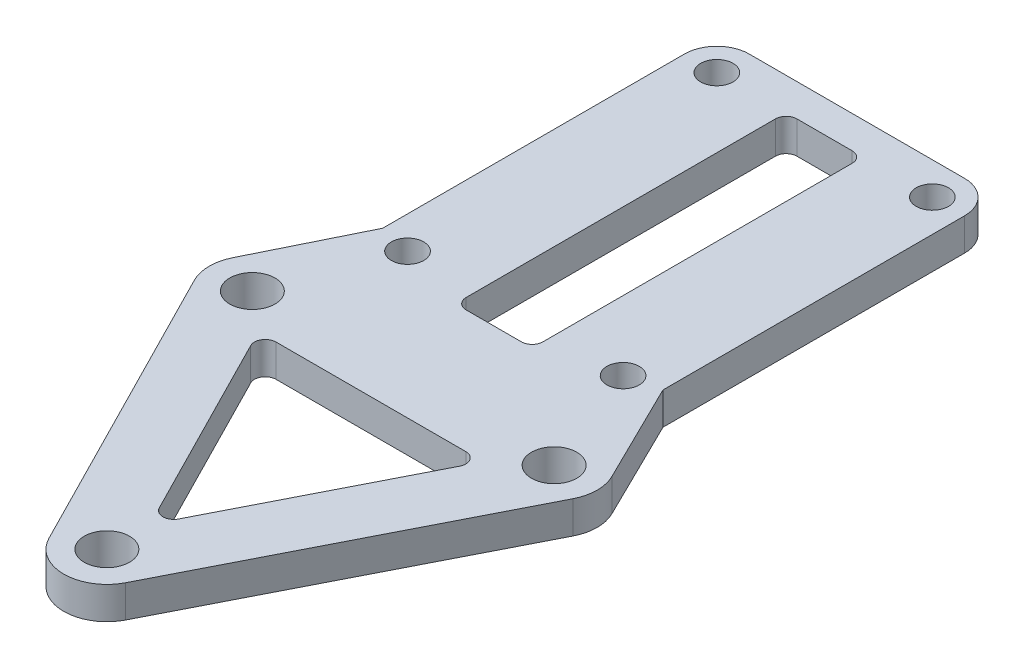
SolidWorks part; units mm, degrees
material "Thornel Mat VMA"
ref_plane "前视基准面" through (0, 0, 0) normal (0, 0, 1) x (1, 0, 0)
ref_plane "上视基准面" through (0, 0, 0) normal (0, 1, 0) x (1, 0, 0)
ref_plane "右视基准面" through (0, 0, 0) normal (1, 0, 0) x (0, 0, -1)
sketch "草图1" plane through (0, 0, 0) normal (0, 1, 0) x (1, 0, 0)
  line L0 (0, 0) -> (0, 27.5) construction
  line L1 (-14, 27.5) -> (14, 27.5) construction
  line L2 (-17.5647, 25.6853) -> (-3.5647, -1.8147)
  line L3 (17.5647, 25.6853) -> (3.5647, -1.8147)
  line L4 (-9.6963, 23.0463) -> (-0.8912, 5.7505)
  line L5 (0.8912, 5.7505) -> (9.6963, 23.0463)
  line L8 (10, 37.9) -> (10, 66.6) construction
  line L9 (-10, 37.9) -> (10, 37.9) construction
  line L10 (-10, 37.9) -> (-10, 66.6) construction
  line L11 (-10, 66.6) -> (10, 66.6) construction
  line L13 (-17.5895, 29.2652) -> (-13, 38.5977)
  line L14 (17.5895, 29.2652) -> (13, 38.5977)
  line L15 (-10, 69.6) -> (10, 69.6)
  line L16 (-13, 38.5977) -> (-13, 66.6)
  line L17 (13, 66.6) -> (13, 38.5977)
  line L18 (-8.8051, 24.5) -> (8.8051, 24.5)
  line L19 (-3.5647, 65.6) -> (-3.5647, 36.9)
  line L20 (-2.5647, 35.9) -> (2.5647, 35.9)
  line L22 (2.5647, 66.6) -> (-2.5647, 66.6)
  line L23 (3.5647, 65.6) -> (3.5647, 36.9)
  circle A0 centre (-14, 27.5) radius 2.1
  circle A1 centre (0, 0) radius 2.1
  circle A2 centre (14, 27.5) radius 2.1
  arc A4 (-3.5647, -1.8147) -> (3.5647, -1.8147) centre (0, 0) ccw
  arc A5 (17.5647, 25.6853) -> (17.5895, 29.2652) centre (14, 27.5) ccw
  circle A7 centre (-10, 66.6) radius 1.5
  circle A8 centre (10, 66.6) radius 1.5
  circle A9 centre (-10, 37.9) radius 1.5
  circle A10 centre (10, 37.9) radius 1.5
  circle A11 centre (-10, 37.9) radius 3 construction
  circle A12 centre (10, 37.9) radius 3 construction
  arc A13 (-10, 69.6) -> (-13, 66.6) centre (-10, 66.6) ccw
  arc A14 (13, 66.6) -> (10, 69.6) centre (10, 66.6) ccw
  arc A15 (-17.5895, 29.2652) -> (-17.5647, 25.6853) centre (-14, 27.5) ccw
  arc A17 (2.5647, 35.9) -> (3.5647, 36.9) centre (2.5647, 36.9) ccw
  arc A18 (-3.5647, 36.9) -> (-2.5647, 35.9) centre (-2.5647, 36.9) ccw
  arc A19 (3.5647, 65.6) -> (2.5647, 66.6) centre (2.5647, 65.6) ccw
  arc A20 (-3.5647, 65.6) -> (-2.5647, 66.6) centre (-2.5647, 65.6) cw
  arc A21 (0.8912, 5.7505) -> (-0.8912, 5.7505) centre (0, 6.2042) cw
  arc A22 (8.8051, 24.5) -> (9.6963, 23.0463) centre (8.8051, 23.5) cw
  arc A23 (-9.6963, 23.0463) -> (-8.8051, 24.5) centre (-8.8051, 23.5) cw
  point P5 (0, 27.5)
  point P44 (3.5647, 35.9)
  point P47 (-3.5647, 35.9)
  point P50 (3.5647, 66.6)
  point P53 (-3.5647, 66.6)
  point P59 (0, 4)
  dimension "D3" = 4.2
  dimension "D4" = 4
  dimension "D8" = 3
  dimension "D9" = 6
  dimension "D12" = 1
  dimension "D13" = 1
  dimension "D1" = 27.5
  dimension "D2" = 14
  dimension "D5" = 28.7
  dimension "D6" = 20
  dimension "D7" = 10.4
  dimension "D10" = 3
  dimension "D11" = 2
extrude "凸台-拉伸1" add sketch "草图1" along normal blind 3
